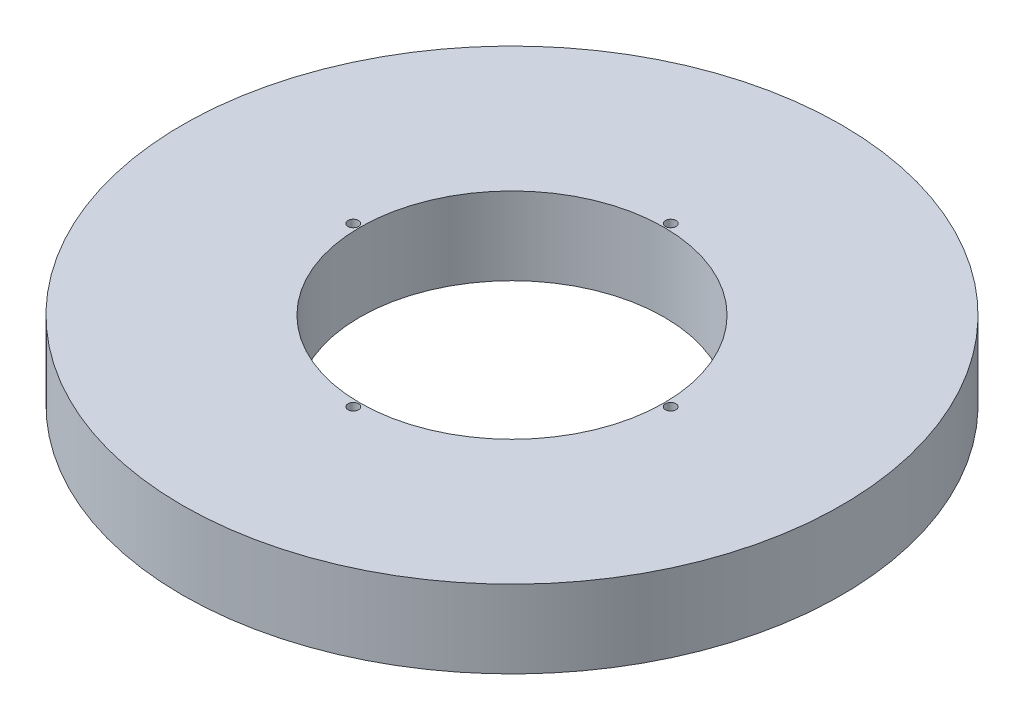
SolidWorks part; units mm, degrees
ref_plane "Front Plane" through (0, 0, 0) normal (0, 0, 1) x (1, 0, 0)
ref_plane "Top Plane" through (0, 0, 0) normal (0, 1, 0) x (1, 0, 0)
ref_plane "Right Plane" through (0, 0, 0) normal (1, 0, 0) x (0, 0, -1)
sketch "Sketch1" plane through (0, 0, 0) normal (0, 1, 0) x (1, 0, 0)
  circle A0 centre (0, 0) radius 97.5
  dimension "FLANGE_OD" = 195
extrude "Boss-Extrude1" add sketch "Sketch1" along normal blind 23
sketch "Sketch2" plane through (0, 0, 0) normal (0, 1, 0) x (1, 0, 0)
  circle A0 centre (0, 0) radius 45
  dimension "BORE_D" = 90
extrude "Cut-Extrude1" cut sketch "Sketch2" along normal through all
sketch "Sketch3" plane through (0, 23, 0) normal (0, 1, 0) x (1, 0, 0)
  circle A0 centre (0, 0) radius 46.9498 construction
  circle A1 centre (-46.9498, 0) radius 1.5559
  dimension "BOLT_D" = 3.1118
  dimension "BOLT_PCD" = 93.8997
extrude "Cut-Extrude2" cut sketch "Sketch3" against normal blind 18.3617
pattern_circular "CirPattern1" count 4 over 360 about axis through (0, 0, 0) along (0, 1, 0) of "Cut-Extrude2"
